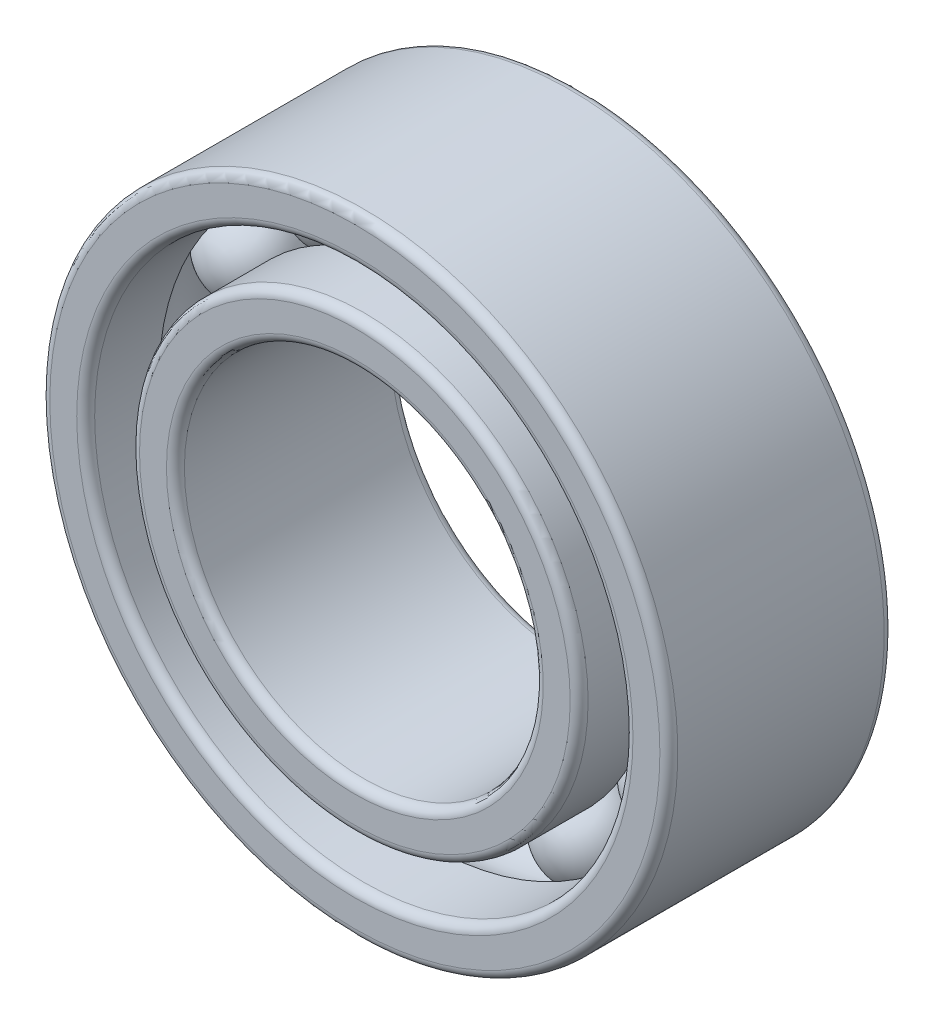
SolidWorks part; units mm, degrees
material "Legierter Stahl"
ref_plane "Ebene vorne" through (0, 0, 0) normal (0, 0, 1) x (1, 0, 0)
ref_plane "Ebene oben" through (0, 0, 0) normal (0, 1, 0) x (1, 0, 0)
ref_plane "Ebene rechts" through (0, 0, 0) normal (1, 0, 0) x (0, 0, -1)
sketch "Skizze1" plane through (0, 0, 0) normal (1, 0, 0) x (0, 0, -1)
  line L0 (0, 0) -> (32.8284, 0) construction
  line L1 (0, 0) -> (0, 22.1569) construction
  line L2 (-1.25, 3.5) -> (1.25, 3.5)
  line L3 (1.25, 3.5) -> (1.25, 3)
  line L4 (1.25, 3) -> (0.433, 3)
  line L5 (0.433, 2.5) -> (1.25, 2.5)
  line L6 (1.25, 2.5) -> (1.25, 2)
  line L7 (1.25, 2) -> (-1.25, 2)
  line L8 (-1.25, 2.5) -> (-1.25, 2)
  line L9 (-0.433, 2.5) -> (-1.25, 2.5)
  line L10 (-1.25, 3) -> (-0.433, 3)
  line L11 (-1.25, 3.5) -> (-1.25, 3)
  line L12 (-0.433, 3) -> (0, 2.75) construction
  line L13 (0, 2.75) -> (0.433, 2.5) construction
  line L14 (-0.5, 2.75) -> (0.5, 2.75)
  circle A0 centre (0, 2.75) radius 0.5
  point P17 (0, 2)
  point P22 (0, 3.5)
  dimension "D1" = 4
  dimension "D6" = 1
  dimension "D2" = 7
  dimension "D3" = 2.5
  dimension "D4" = 5
  dimension "D5" = 6
revolve "Rotation1" add sketch "Skizze1" angle 360 about L0 region at (0, 3.2707, 0) region at (0, 2.2293, 0)
revolve "Rotation3" add sketch "Skizze1<5>" angle 360 about L14 region at (0, 2.9622, 0)
sketch "Skizze1<5>" plane through (0, 0, 0) normal (1, 0, 0) x (0, 0, -1) same geometry as "Skizze1"
ref_axis "Achse1" through (0, 0, -1.25) along (0, 0, 1)
pattern_circular "Kreismuster4" count 12 over 360 about axis through (0, 0, -1.25) along (0, 0, 1) of bodies 110
fillet "Verrundung1" radius 0.1 4 edges at (3, 0, -1.25) (3, 0, 1.25) (3.5, 0, -1.25) (3.5, 0, 1.25)
fillet "Verrundung2" radius 0.1 4 edges at (2.5, 0, -1.25) (2, 0, -1.25) (2.5, 0, 1.25) (2, 0, 1.25)
